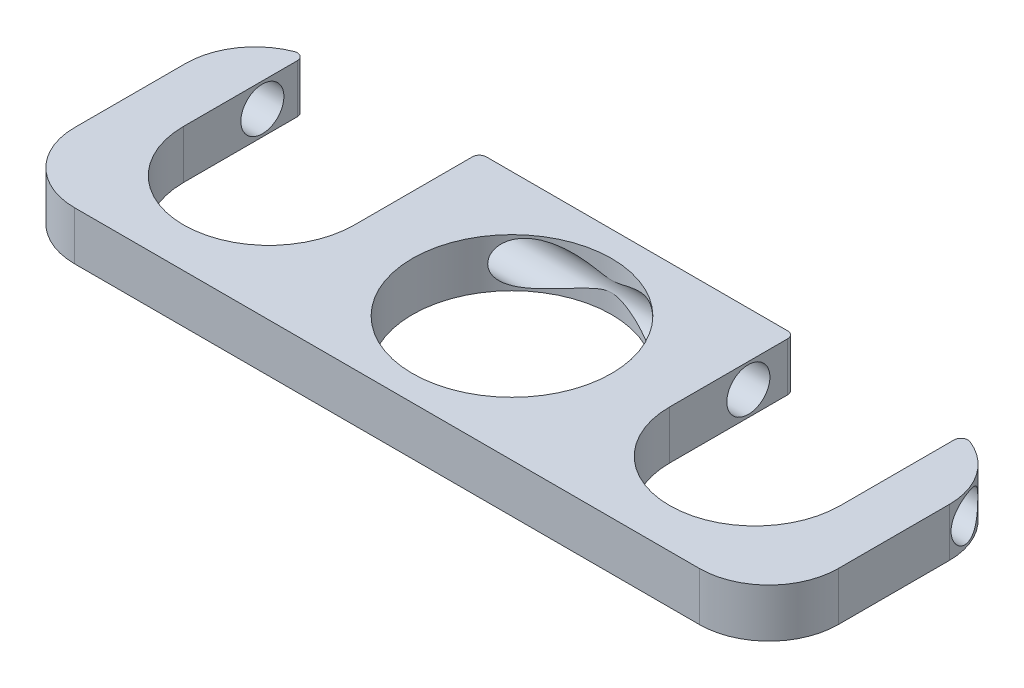
SolidWorks part; units mm, degrees
material "PLA"
ref_plane "Front Plane" through (0, 0, 0) normal (0, 0, 1) x (1, 0, 0)
ref_plane "Top Plane" through (0, 0, 0) normal (0, 1, 0) x (1, 0, 0)
ref_plane "Right Plane" through (0, 0, 0) normal (1, 0, 0) x (0, 0, -1)
sketch "Sketch1" plane through (0, 0, 0) normal (0, 1, 0) x (1, 0, 0)
  line L0 (0, 18) -> (0, -18) construction
  line L1 (-45, -18) -> (45, -18)
  line L2 (-55, -8) -> (-55, 8)
  line L3 (-45, 18) -> (45, 18)
  line L4 (55, -8) -> (55, 8)
  line L5 (-55, 0) -> (55, 0) construction
  line L7 (-55, 18) -> (0, 18) construction
  line L8 (0, 18) -> (-27.5, 18) construction
  circle A0 centre (0, 0) radius 14.35
  arc A2 (45, 18) -> (55, 8) centre (45, 8) cw
  arc A3 (45, -18) -> (55, -8) centre (45, -8) ccw
  arc A4 (-45, -18) -> (-55, -8) centre (-45, -8) cw
  arc A5 (-55, 8) -> (-45, 18) centre (-45, 8) cw
  point P0 (0, 0)
  point P17 (55, -18)
  point P20 (-55, -18)
  point P24 (0, 0)
  dimension "D3" = 28.7
  dimension "D5" = 10
  dimension "D1" = 36
  dimension "D2" = 110
extrude "Boss-Extrude1" add sketch "Sketch1" along normal blind 7
sketch "Sketch2" plane through (0, 7, 0) normal (0, 1, 0) x (1, 0, 0)
  line L1 (-22.7, 0) -> (-22.7, 18)
  line L2 (45, 18) -> (-45, 18) construction
  line L7 (-47.3, 0) -> (-47.3, 18)
  line L9 (-14.25, 0) -> (-22.7, 0) construction
  line L10 (-55, 0) -> (55, 0) construction
  line L11 (-55, 8) -> (-55, -8) construction
  line L12 (55, -8) -> (55, 8) construction
  line L13 (-47.3, 18) -> (-22.7, 18)
  circle A0 centre (-35, 0) radius 12.3 construction
  circle A1 centre (0, 0) radius 14.25 construction
  arc A3 (-47.3, 0) -> (-22.7, 0) centre (-35, 0) ccw
  dimension "D1" = 24.6
  dimension "D2" = 28.5
  dimension "D3" = 8.45
ref_axis "Axis1" through (0, 0, 0) along (0, 1, 0)
ref_plane "Plane1" through (0, 0, 0) normal (-1, 0, 0) x (0, 1, 0)
extrude "Cut-Extrude1" cut sketch "Sketch2" against normal blind 10
sketch "Sketch3" plane through (-22.7, 0, 0) normal (-1, 0, 0) x (0, 0, 1)
  line L0 (-18, 3.5) -> (0, 3.5) construction
  line L1 (-18, 0) -> (-18, 7) construction
  line L2 (0, 0) -> (0, 38.1946) construction
  line L3 (0, 3.5) -> (-11.3487, 7) construction
  line L4 (0, 7) -> (-18, 7) construction
  line L5 (-11.3487, 7) -> (-11.3487, 0) construction
  line L6 (-18, 0) -> (0, 0) construction
  circle A0 centre (-11.3487, 3.5) radius 3.1
  dimension "D1" = 6.2
extrude "Cut-Extrude2" cut sketch "Sketch3" against normal through all both and the other way through all
fillet "Fillet2" radius 1 1 edges at (-47.3, 3.5, -17.7319) type face fillet first side face at (-47.3, 3.5, -8.2487) second side face at (-52.6618, 3.873, -14.4262)
fillet "Fillet3" radius 1 1 edges at (-22.7, 3.5, -18) type face fillet first side face at (-22.7, 3.5, -14.4487) second side face at (11.15, 3.5, -18)
mirror "Mirror5" about plane through (0, 0, 0) normal (-1, 0, 0) of "Cut-Extrude1"
fillet "Fillet5" radius 1 1 edges at (47.3, 3.5, -17.7319) type face fillet first side face at (47.3, 3.5, -8.866) second side face at (52.6618, 3.127, -14.4262)
fillet "Fillet7" radius 1 1 edges at (22.7, 3.5, -18) type face fillet first side face at (22.7, 3.5, -9) second side face at (0.5, 3.5, -18)
